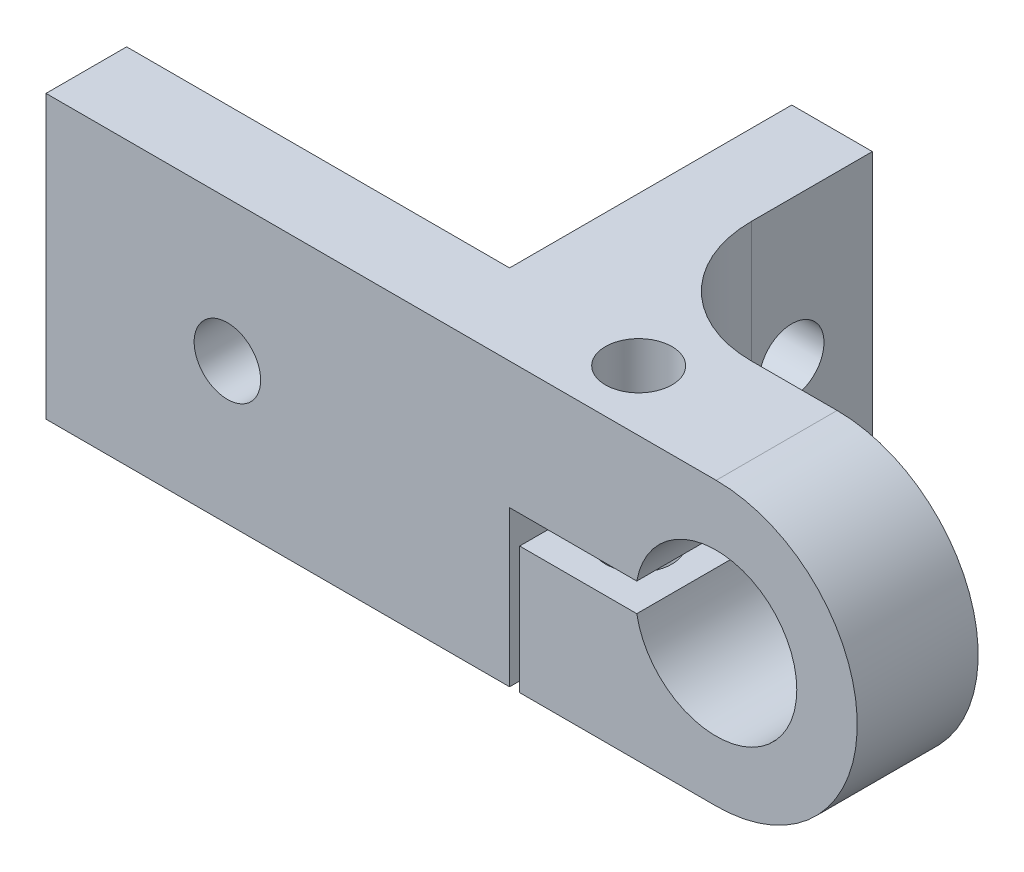
SolidWorks part; units mm, degrees
ref_plane "Plano frontal" through (0, 0, 0) normal (0, 0, 1) x (1, 0, 0)
ref_plane "Plano superior" through (0, 0, 0) normal (0, 1, 0) x (1, 0, 0)
ref_plane "Plano direito" through (0, 0, 0) normal (1, 0, 0) x (0, 0, -1)
sketch "Esboço2" plane through (0, 0, 0) normal (0, 0, 1) x (1, 0, 0)
  line L0 (0, 7) -> (-33.25, 7)
  line L1 (-33.25, 7) -> (-33.25, -7)
  line L2 (-33.25, -7) -> (-10.25, -7)
  line L3 (-4, 0) -> (-10, 0) construction
  line L4 (-10, 0) -> (-10, -7) construction
  line L5 (-3.9383, 0.7) -> (-10.25, 0.7)
  line L6 (-10.25, 0.7) -> (-10.25, -7)
  line L7 (-3.9383, -0.7) -> (-9.75, -0.7)
  line L8 (-9.75, -0.7) -> (-9.75, -7)
  line L11 (-9.75, -7) -> (0, -7)
  arc A0 (-3.9383, -0.7) -> (-3.9383, 0.7) centre (0, 0) ccw
  arc A1 (0, -7) -> (0, 7) centre (0, 0) ccw
  circle A2 centre (-24.25, 0) radius 1.65
  point P19 (0, 0)
  point P20 (-33.25, 0)
  dimension "D1" = 8
  dimension "D3" = 7
  dimension "D8" = 3.3
  dimension "D2" = 10
  dimension "D6" = 23
  dimension "D7" = 9
  dimension "D4" = 0.7
  dimension "D5" = 0.7
  dimension "D9" = 0.5
extrude "Ressalto-extrusão1" add sketch "Esboço2" along normal blind 18
sketch "Esboço3" plane through (0, -7, 0) normal (0, -1, 0) x (1, 0, 0)
  line L0 (-33.25, 14) -> (-14.25, 14)
  line L1 (-33.25, 18) -> (-33.25, 0) construction
  line L2 (-14.25, 14) -> (-14.25, 0)
  line L3 (-33.25, 0) -> (-10.25, 0) construction
  line L4 (-14.25, 0) -> (-33.25, 0)
  line L5 (-33.25, 0) -> (-33.25, 14)
  line L6 (7, 12) -> (-4.25, 12)
  line L7 (7, 0) -> (7, 18) construction
  line L8 (-10.25, 0) -> (7, 0)
  line L9 (7, 0) -> (7, 12)
  line L10 (-10.25, 0) -> (-10.25, 6)
  line L11 (-33.25, 18) -> (-10.25, 18) construction
  line L12 (-9.75, 18) -> (0, 18) construction
  line L13 (-3.9383, 18) -> (-9.75, 18) construction
  line L14 (-2.8316, 18) -> (-2.8316, 12) construction
  arc A0 (-10.25, 6) -> (-4.25, 12) centre (-4.25, 6) cw
  circle A1 centre (-6.8441, 15) radius 1.65
  point P10 (-2.8316, 15)
  point P28 (-6.8441, 18)
  dimension "D1" = 6
  dimension "D6" = 3.3
  dimension "D2" = 4
  dimension "D3" = 6
  dimension "D4" = 4
  dimension "D5" = 19
extrude "Corte-extrusão1" cut sketch "Esboço3" against normal through all and the other way through all
sketch "Esboço4" plane through (-14.25, 0, 0) normal (-1, 0, 0) x (0, 0, 1)
  line L0 (14, 7) -> (14, -7) construction
  line L1 (0, 7) -> (0, -7) construction
  circle A0 centre (4, 0) radius 1.6
  point P4 (0, 0)
  point P7 (0, 0)
  dimension "D2" = 3.2
  dimension "D1" = 10
extrude "Corte-extrusão2" cut sketch "Esboço4" against normal blind 18
